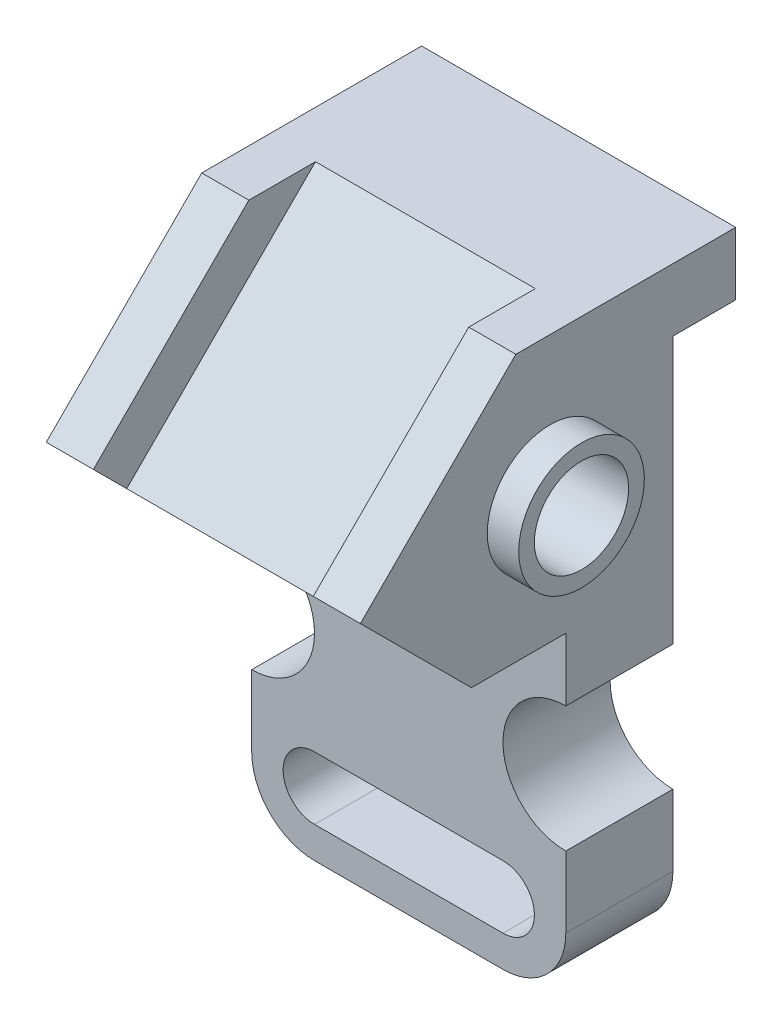
SolidWorks part; units mm, degrees
ref_plane "Спереди" through (0, 0, 0) normal (0, 0, 1) x (1, 0, 0)
ref_plane "Сверху" through (0, 0, 0) normal (0, 1, 0) x (1, 0, 0)
ref_plane "Справа" through (0, 0, 0) normal (1, 0, 0) x (0, 0, -1)
sketch "Эскиз1" plane through (0, 0, 0) normal (0, 0, 1) x (1, 0, 0)
  line L0 (0, 0) -> (0, -50.4929) construction
  line L1 (0, 0) -> (50, 0)
  line L2 (50, 0) -> (50, 42.6536)
  line L3 (50, 102.6536) -> (0, 102.6536)
  line L4 (50, 82.6536) -> (50, 102.6536)
  line L5 (50, 20) -> (0, 20) construction
  line L6 (30, 30) -> (0, 30)
  line L7 (30, 10) -> (0, 10)
  line L8 (50, 102.6536) -> (50, 187.5536)
  line L9 (50, 187.5536) -> (0, 187.5536)
  line L10 (0, 10) -> (0, 0)
  line L11 (0, 102.6536) -> (0, 30)
  line L12 (0, 187.5536) -> (0, 102.6536)
  arc A0 (50, 82.6536) -> (50, 42.6536) centre (50, 62.6536) ccw
  arc A1 (30, 10) -> (30, 30) centre (30, 20) ccw
  dimension "D4" = 40
  dimension "D5" = 20
  dimension "D1" = 102.6536
  dimension "D2" = 100
  dimension "D3" = 40
  dimension "D6" = 20
  dimension "D7" = 60
  dimension "D8" = 84.9
extrude "Бобышка-Вытянуть1" add sketch "Эскиз1" along normal blind 34.1 contours A1 L7 L10 L1 L2 A0 L4 L3 L11 L6 region at (23.4451, 55.7567, 0)
fillet "Скругление2" radius 20 1 edges at (50, 0, 17.05)
extrude "Бобышка-Вытянуть3" add sketch "Эскиз1<5>" along normal blind 34.1 contours L9 L12 L3 L8 region at (25, 145.1036, 0)
sketch "Эскиз1<5>" plane through (0, 0, 0) normal (0, 0, 1) x (1, 0, 0) same geometry as "Эскиз1"
sketch "Эскиз4" plane through (50, 0, 0) normal (1, 0, 0) x (0, 0, -1)
  line L0 (0, 187.5536) -> (20, 187.5536)
  line L1 (20, 187.5536) -> (20, 167.5536)
  line L2 (20, 167.5536) -> (0, 167.5536)
  line L3 (0, 82.6536) -> (0, 187.5536) construction
  line L4 (0, 187.5536) -> (0, 167.5536)
  dimension "D1" = 20
  dimension "D2" = 20
extrude "Бобышка-Вытянуть4" add sketch "Эскиз4" against normal up to surface (50 mm away) up to face at (0, 108.7768, 17.05)
sketch "Эскиз5" plane through (50, 0, 0) normal (1, 0, 0) x (0, 0, -1)
  line L0 (-34.1, 187.5536) -> (-50, 187.5536)
  line L1 (20, 167.5536) -> (20, 187.5536) construction
  line L2 (-50, 187.5536) -> (-99.4975, 138.0561)
  line L3 (-99.4975, 138.0561) -> (-64.1421, 102.7008)
  line L4 (-64.1421, 102.7008) -> (-34.1, 102.7008)
  line L5 (-34.1, 82.6536) -> (-34.1, 187.5536) construction
  line L6 (-34.1, 102.7008) -> (-34.1, 187.5536)
  dimension "D1" = 70
  dimension "D2" = 135
  dimension "D3" = 50
  dimension "D4" = 70
extrude "Бобышка-Вытянуть5" add sketch "Эскиз5" against normal up to surface (50 mm away) up to face at (0, 128.3691, 4.7)
sketch "Эскиз7" plane through (50, 0, 0) normal (1, 0, 0) x (0, 0, -1)
  line L0 (-64.1421, 102.7008) -> (-34.1, 102.7008) construction
  line L2 (0, 82.6536) -> (0, 167.5536) construction
  circle A0 centre (-39.1, 142.7008) radius 15
  point P4 (0, 0)
  point P6 (0, 132.0185)
  dimension "D3" = 30
  dimension "D1" = 40
  dimension "D2" = 39.1
extrude "Вырез-Вытянуть1" cut sketch "Эскиз7" against normal through all and the other way through all
sketch "Эскиз8" plane through (0, 19.2793, -19.2793) normal (0, -0.7071, 0.7071) x (1, 0, 0)
  line L0 (35, 167.9758) -> (35, 152.9758)
  line L1 (0, 167.9758) -> (50, 167.9758) construction
  line L2 (35, 152.9758) -> (0, 152.9758)
  line L3 (0, 117.9758) -> (0, 167.9758) construction
  line L4 (50, 167.9758) -> (50, 118.4783) construction
  line L5 (0, 167.9758) -> (0, 152.9758)
  line L6 (35, 167.9758) -> (0, 167.9758)
  dimension "D1" = 15
  dimension "D2" = 15
extrude "Вырез-Вытянуть2" cut sketch "Эскиз8" against normal through all
mirror "Зеркальное отражение1" about plane through (0, 0, 34.1) normal (1, 0, 0) of "Бобышка-Вытянуть1", "Скругление2", "Бобышка-Вытянуть4", "Вырез-Вытянуть1", "Бобышка-Вытянуть3", "Бобышка-Вытянуть5", "Вырез-Вытянуть2"
sketch "Эскиз13" plane through (50, 0, 0) normal (1, 0, 0) x (0, 0, -1)
  circle A0 centre (-39.1, 142.7008) radius 20
  point P4 (-39.1, 142.7008)
  dimension "D1" = 40
extrude "Бобышка-Вытянуть6" add sketch "Эскиз13" along normal blind 10
sketch "Эскиз15" plane through (50, 0, 0) normal (-1, 0, 0) x (0, 0, 1)
  circle A0 centre (39.1, 142.7008) radius 15
  circle A1 centre (39.1, 142.7008) radius 20 construction
  dimension "D1" = 30
extrude "Вырез-Вытянуть3" cut sketch "Эскиз15" against normal through all both and the other way through all
